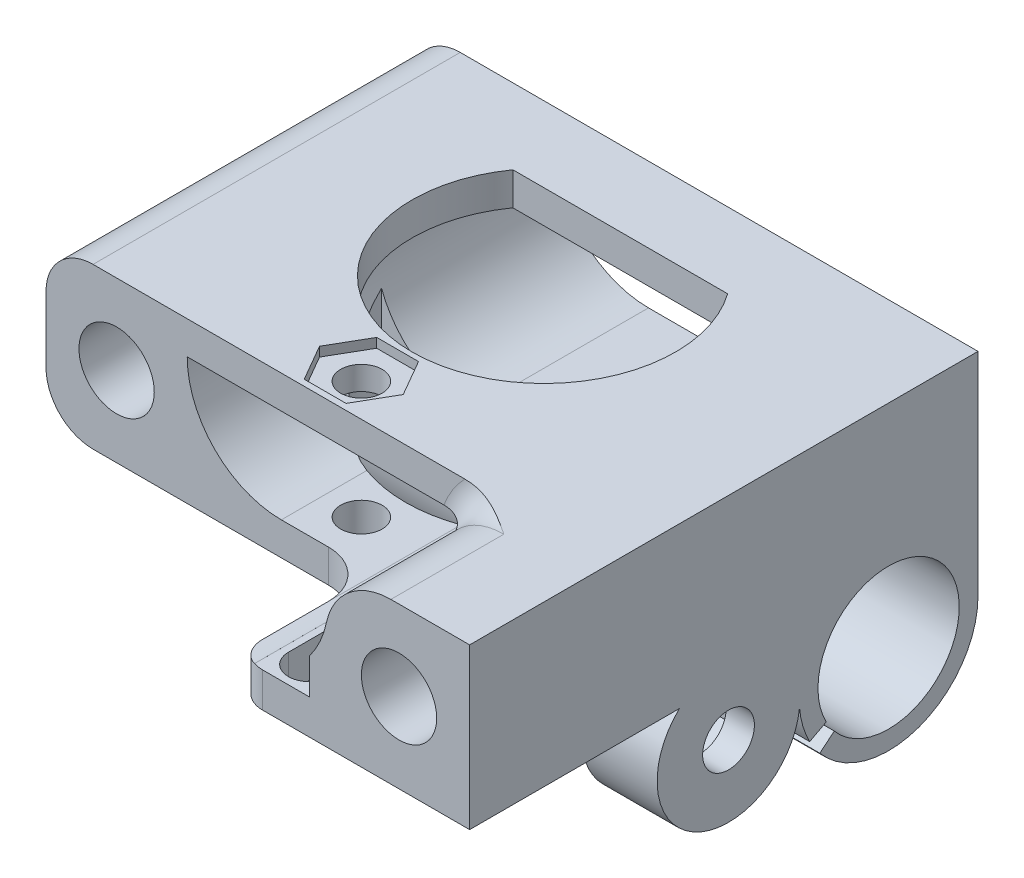
SolidWorks part; units mm, degrees
material "ABS generico"
ref_plane "Front Plane" through (0, 0, 0) normal (0, 0, 1) x (1, 0, 0)
ref_plane "Top Plane" through (0, 0, 0) normal (0, 1, 0) x (1, 0, 0)
ref_plane "Right Plane" through (0, 0, 0) normal (1, 0, 0) x (0, 0, -1)
sketch "Sketch1" plane through (0, 0, 0) normal (1, 0, 0) x (0, 0, -1)
  line L1 (21.1236, -26.9641) -> (22.8813, -26.0274)
  line L3 (23.7305, -27.2923) -> (22.1984, -28.5649)
  line L4 (20.0416, -23.294) -> (20.0416, -17)
  line L8 (39, 0) -> (0, 0)
  line L12 (0, -17) -> (0, 0)
  line L13 (0, -17) -> (20.0416, -17)
  line L15 (39, -22.5) -> (39, 0)
  line L19 (16.5, -29.4282) -> (20.0416, -23.294) construction
  line L20 (8.5, -29.4282) -> (16.5, -29.4282) construction
  line L21 (4.5, -22.5) -> (8.5, -29.4282) construction
  line L22 (4.5, -17) -> (4.5, -22.5) construction
  arc A0 (23.7305, -27.2923) -> (22.8813, -26.0274) centre (29.5041, -22.4988) ccw
  arc A1 (20.0416, -23.294) -> (21.1236, -26.9641) centre (29.5041, -22.4988) ccw
  arc A2 (22.1984, -28.5649) -> (39, -22.5) centre (29.5041, -22.4988) ccw
  circle A5 centre (12.5, -22.5) radius 2.75 construction
  dimension "D2" = 7.5042
  dimension "D3" = 9.4959
  dimension "D1" = 39
  dimension "D4" = 17
extrude "Extrude1" add sketch "Sketch1" against normal blind 60
sketch "Sketch2" plane through (0, 0, 0) normal (0, 0, 1) x (1, 0, 0)
  line L0 (-60, -8.5) -> (0, -8.5) construction
  line L1 (-60, 0) -> (-60, -17) construction
  line L2 (0, 0) -> (0, -17) construction
  line L3 (-30, 1.8171) -> (-30, -40.9837) construction
  line L5 (-15, -13.5) -> (-45, -13.5)
  line L6 (-15, -13.5) -> (-15, -3.5)
  line L7 (-15, -3.5) -> (-45, -3.5)
  line L8 (-45, -13.5) -> (-45, -3.5)
  line L9 (-15, -13.5) -> (-45, -3.5) construction
  line L10 (-15, -3.5) -> (-45, -13.5) construction
  circle A0 centre (-52.5, -8.5) radius 4
  circle A1 centre (-7.5, -8.5) radius 4
  point P12 (-30, -8.5)
  dimension "D1" = 8
  dimension "D2" = 22.5
  dimension "D3" = 7.5
  dimension "D4" = 10
  dimension "D5" = 30
extrude "Extrude2" cut sketch "Sketch2" against normal up to surface (39 mm away) up to face at (-30, -11.25, -39)
sketch "Sketch3" plane through (0, 0, 0) normal (0, 0, 1) x (1, 0, 0)
  line L0 (-52.5, -8.5) -> (-7.5, -8.5) construction
  line L1 (-52.5, -8.5) -> (-52.5, 8.8734) construction
  line L2 (-32.5, -8.5) -> (-32.5, 8.8734) construction
  dimension "D1" = 20
sketch "Sketch4" plane through (0, 0, 0) normal (1, 0, 0) x (0, 0, -1)
  line L0 (7.2804, -17) -> (20.0416, -17)
  line L1 (12.5, -17.9967) -> (8.6, -20.2483) construction
  line L2 (8.6, -20.2483) -> (8.6, -24.7517) construction
  line L3 (8.6, -24.7517) -> (12.5, -27.0033) construction
  line L4 (12.5, -27.0033) -> (16.4, -24.7517) construction
  line L5 (16.4, -24.7517) -> (16.4, -20.2483) construction
  line L6 (16.4, -20.2483) -> (12.5, -17.9967) construction
  line L7 (0, -17) -> (20.0416, -17) construction
  line L8 (20.0416, -17) -> (20.0817, -22.3872)
  circle A0 centre (12.5, -22.5) radius 3.9 construction
  arc A1 (7.2804, -17) -> (20.0817, -22.3872) centre (12.5, -22.5) ccw
  dimension "D1" = 7.8
extrude "Extrude3" add sketch "Sketch4" against normal blind 8
sketch "Sketch5" plane through (0, 0, 0) normal (1, 0, 0) x (0, 0, -1)
  circle A0 centre (12.5, -22.5) radius 2.75
  dimension "D1" = 5.5
extrude "Extrude4" cut sketch "Sketch5" against normal up to surface (8 mm away) up to face at (-8, -22.1484, -14.2839)
sketch "Sketch6" plane through (-8, 0, 0) normal (-1, 0, 0) x (0, 0, 1)
  line L1 (-12.5, -17.8812) -> (-16.5, -20.1906)
  line L2 (-16.5, -20.1906) -> (-16.5, -24.8094)
  line L3 (-16.5, -24.8094) -> (-12.5, -27.1188)
  line L4 (-12.5, -27.1188) -> (-8.5, -24.8094)
  line L5 (-8.5, -24.8094) -> (-8.5, -20.1906)
  line L6 (-8.5, -20.1906) -> (-12.5, -17.8812)
extrude "Extrude5" cut sketch "Sketch6" against normal blind 5
sketch "Sketch7" plane through (0, 0, 0) normal (0, 1, 0) x (1, 0, 0)
  line L2 (-31, -370.8295) -> (-31, 97.9462) construction
  line L6 (-30.9897, -180.6724) -> (-30.9897, -405.4164) construction
  circle A0 centre (-31, 4.5) radius 2.2
extrude "Extrude6" cut sketch "Sketch7" against normal up to surface (17 mm away) up to face at (-22.6667, -17, -9.1073)
sketch "Sketch8" plane through (0, 0, -39) normal (0, 0, -1) x (-1, 0, 0)
  line L0 (7.5, -8.5) -> (52.5, -8.5) construction
  line L1 (30, -8.5) -> (30, 3.0319) construction
  circle A0 centre (7.5, -8.5) radius 4.201
  circle A1 centre (52.5, -8.5) radius 1.25
  circle A2 centre (7.5, -8.5) radius 1.25
  circle A3 centre (52.5, -8.5) radius 4.201
  dimension "D1" = 2.5
extrude "Extrude7" add sketch "Sketch8" against normal blind 9
sketch "Sketch10" plane through (-60, 0, 0) normal (-1, 0, 0) x (0, 0, 1)
  line L1 (-20.0416, -17) -> (-39.247, -17)
  line L2 (-20.0416, -17) -> (-20.0416, -32.1139)
  line L3 (-20.0416, -32.1139) -> (-39.247, -32.1139)
  line L4 (-39.247, -17) -> (-39.247, -32.1139)
extrude "Extrude8" cut sketch "Sketch10" against normal blind 10
fillet "Fillet9" radius 10 2 edges at (-55, -17, -24.3976) (-55, -17, -34.6107)
fillet "Fillet11" radius 5 1 edges at (-60, 0, -19.5)
fillet "Fillet12" radius 5 5 edges at (-60, -17, -38.3198) (-60, -16.7094, -35.2462) (-60, -14.9946, -29.5041) (-60, -16.7094, -23.7621) (-60, -17, -10.6843)
sketch "Sketch12" plane through (0, 0, 0) normal (0, 0, 1) x (1, 0, 0)
  line L0 (-15, -13.5) -> (-15, 2.5343) construction
  line L1 (0, 0) -> (-20.7492, 0) construction
  line L2 (-55, 0) -> (0, 0) construction
  line L3 (-45, -13.5) -> (-15, -13.5) construction
  line L4 (-15, 0) -> (0, 0)
  line L5 (-11.5, -8.5) -> (-11.5, 2.5343) construction
  line L6 (-15, -17) -> (0, -17)
  line L7 (0, 0) -> (0, -17)
  line L8 (-15, -17) -> (-25, -17)
  line L9 (-25, -13.5) -> (-15, -13.5)
  line L10 (-15, -13.5) -> (-15, 0)
  line L11 (-25, -17) -> (-25, -13.5)
  circle A0 centre (-7.5, -8.5) radius 4
  point P21 (-14.5, -8.5)
  point P22 (-14.5, 2.5343)
  dimension "D3" = 8
  dimension "D1" = 10
extrude "Extrude10" add sketch "Sketch12" along normal blind 15
sketch "Sketch13" plane through (0, -17, 0) normal (0, -1, 0) x (1, 0, 0)
  line L0 (0, 10.5645) -> (0, 23.7024) construction
  line L1 (0, 15) -> (0, -7.2804) construction
  line L2 (-20, -5.2455) -> (-20, 23.7024) construction
  line L3 (-20, 10.5645) -> (-20, 23.7024) construction
  line L4 (-25, 0) -> (-9.3359, 0) construction
  line L5 (-25, 15) -> (-25, 0) construction
  line L6 (-20, 12) -> (-20, -3) construction
  line L7 (-17.75, 12) -> (-17.75, -3)
  line L8 (-22.25, 12) -> (-22.25, -3)
  line L9 (-25, 15) -> (0, 15) construction
  arc A0 (-17.75, 12) -> (-22.25, 12) centre (-20, 12) ccw
  arc A1 (-22.25, -3) -> (-17.75, -3) centre (-20, -3) ccw
  point P14 (-20, 4.5)
  dimension "D2" = 3
  dimension "D1" = 5
extrude "Extrude11" cut sketch "Sketch13" against normal up to surface (3.5 mm away) up to face at (-28.8, -13.5, -4.5)
sketch "Sketch14" plane through (0, -17, 0) normal (0, -1, 0) x (1, 0, 0)
  line L1 (-12, -10.2024) -> (-12, 22.3262) construction
  line L3 (-10.5, -3) -> (-10.5, 12)
  line L4 (-13.5, 12) -> (-13.5, -3)
  arc A2 (-10.5, 12) -> (-13.5, 12) centre (-12, 12) ccw
  arc A3 (-13.5, -3) -> (-10.5, -3) centre (-12, -3) ccw
extrude "Extrude12" cut sketch "Sketch14" against normal blind 2
chamfer "Chamfer1" distance 1 angle 45 4 edges at (-13.5, -17, 4.5) (-12, -17, -4.5) (-12, -17, 13.5) (-10.5, -17, 4.5)
fillet "Fillet15" radius 3 1 edges at (-25, -15.25, 15)
sketch "Sketch15" plane through (0, 0, 0) normal (0, 1, 0) x (1, 0, 0)
  line L0 (-50, 22.8813) -> (0, 22.8813) construction
  line L1 (-41.4058, 31) -> (-18.5942, 31)
  arc A0 (-41.4058, 31) -> (-18.5942, 31) centre (-30, 22.8813) ccw
extrude "Extrude13" cut sketch "Sketch15" against normal blind 9
fillet "Fillet18" radius 1 4 edges at (-13.5, -15, 4.5) (-12, -15, 13.5) (-10.5, -15, 4.5) (-12, -15, -4.5)
fillet "Fillet19" radius 11 4 edges at (-13.5, -16, 4.5) (-12, -16, 13.5) (-10.5, -16, 4.5) (-12, -16, -4.5)
fillet "Fillet20" radius 10 1 edges at (-45, -13.5, -19.5)
sketch "Sketch16" plane through (0, -17, 0) normal (0, -1, 0) x (1, 0, 0)
  line L0 (-30, -8.881) -> (-30, -22.8813) construction
  line L1 (-44.4017, -20.0416) -> (-15.5983, -20.0416)
  arc A1 (-15.5983, -20.0416) -> (-44.4017, -20.0416) centre (-30, -22.8813) ccw
extrude "Extrude14" cut sketch "Sketch16" against normal up to surface (13.5 mm away) up to face at (-30, -3.5, -19.9405)
fillet "Fillet21" radius 10 1 edges at (-15, -13.5, -12)
fillet "Fillet22" radius 5 1 edges
sketch "Sketch17" plane through (0, 0, 0) normal (0, 1, 0) x (1, 0, 0)
  line L7 (-35.4444, 4.5) -> (-33.2222, 0.651)
  line L8 (-33.2222, 0.651) -> (-28.7778, 0.651)
  line L9 (-28.7778, 0.651) -> (-26.5556, 4.5)
  line L10 (-26.5556, 4.5) -> (-28.7778, 8.349)
  line L11 (-28.7778, 8.349) -> (-33.2222, 8.349)
  line L12 (-33.2222, 8.349) -> (-35.4444, 4.5)
  circle A0 centre (-31, 4.5) radius 3.849 construction
extrude "Cut-Extrude1" cut sketch "Sketch17" against normal blind 1
sketch "Sketch18" plane through (0, -3.5, 0) normal (0, -1, 0) x (1, 0, 0)
  line L0 (-20, -5.25) -> (-20, 17.0853) construction
  line L1 (-17, -3) -> (-17, 17.0853)
  line L2 (-23, -3) -> (-23, 17.0853)
  line L3 (-16.6454, -3) -> (-23.5438, -3) construction
  line L4 (-23, 17.0853) -> (-17, 17.0853)
  line L5 (-23, -5.25) -> (-23, 17.0853) construction
  line L6 (-17, -5.25) -> (-17, 17.0853) construction
  arc A0 (-22.25, -3) -> (-17.75, -3) centre (-20, -3) ccw construction
  arc A1 (-23, -3) -> (-17, -3) centre (-20, -3) ccw
  dimension "D1" = 3
  dimension "D2" = 3
extrude "Cut-Extrude2" cut sketch "Sketch18" along normal blind 9.8
fillet "Fillet33" radius 7 1 edges
fillet "Fillet34" radius 3 1 edges at (-11.8642, -0.9378, 0)
